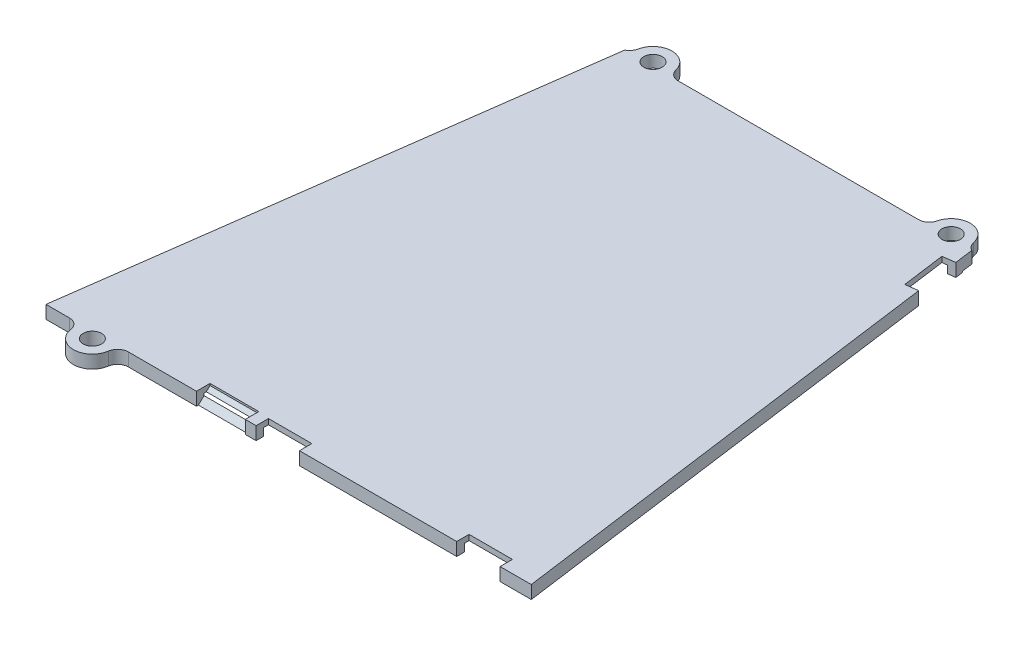
SolidWorks part; units mm, degrees
ref_plane "前视基准面" through (0, 0, 0) normal (0, 0, 1) x (1, 0, 0)
ref_plane "上视基准面" through (0, 0, 0) normal (0, 1, 0) x (1, 0, 0)
ref_plane "右视基准面" through (0, 0, 0) normal (1, 0, 0) x (0, 0, -1)
other "Configuration Table"
sketch "草图1" plane through (0, 0, 0) normal (0, 1, 0) x (1, 0, 0)
  line L0 (0, 0) -> (12.75, 94)
  line L1 (12.75, 94) -> (76.75, 94)
  line L2 (76.75, 94) -> (89.5, 0)
  line L3 (89.5, 0) -> (0, 0)
  line L4 (44.75, 94) -> (44.75, 0) construction
  dimension "D1" = 89.5
  dimension "D2" = 64
  dimension "D3" = 94
extrude "凸台-拉伸1" add sketch "草图1" along normal blind 1
sketch "草图2" plane through (0, 0, 0) normal (0, -1, 0) x (1, 0, 0)
  line L8 (87.8973, -1.4) -> (1.6027, -1.4)
  line L9 (1.6027, -1.4) -> (13.9729, -92.6)
  line L10 (13.9729, -92.6) -> (75.5271, -92.6)
  line L11 (75.5271, -92.6) -> (87.8973, -1.4)
  line L12 (87.8973, -1.4) -> (1.6027, -1.4)
  line L13 (1.6027, -1.4) -> (13.9729, -92.6)
  line L14 (13.9729, -92.6) -> (75.5271, -92.6)
  line L15 (75.5271, -92.6) -> (87.8973, -1.4)
  line L16 (89.5, 0) -> (0, 0)
  line L17 (0, 0) -> (12.75, -94)
  line L18 (12.75, -94) -> (76.75, -94)
  line L19 (76.75, -94) -> (89.5, 0)
  line L20 (89.5, 0) -> (0, 0)
  line L21 (0, 0) -> (12.75, -94)
  line L22 (12.75, -94) -> (76.75, -94)
  line L23 (76.75, -94) -> (89.5, 0)
  dimension "D1" = 1.4
  dimension "D2" = 0
extrude "凸台-拉伸2" add sketch "草图2" along normal blind 1.4
sketch "草图3" plane through (0, 1, 0) normal (0, 1, 0) x (1, 0, 0)
  line L0 (44.75, 0) -> (44.75, 94) construction
  line L1 (0, 0) -> (89.5, 0) construction
  line L2 (76.75, 94) -> (12.75, 94) construction
  line L3 (6.25, -1.2) -> (6.25, 0)
  line L4 (13.25, -1.2) -> (13.25, 0)
  line L5 (13.25, 0) -> (10.9542, 0)
  line L6 (8.5458, 0) -> (6.25, 0)
  line L7 (13.75, 94.7) -> (13.75, 94)
  line L8 (13.8207, 94) -> (15.7008, 94)
  line L9 (20.75, 94) -> (20.75, 94.7)
  line L10 (13.75, 94) -> (13.8207, 94)
  line L11 (18.7992, 94) -> (20.75, 94)
  line L12 (68.75, 94.7) -> (68.75, 94)
  line L13 (68.75, 94) -> (70.7008, 94)
  line L14 (75.75, 94) -> (75.75, 94.7)
  line L15 (73.7992, 94) -> (75.75, 94)
  arc A0 (8.5458, 0) -> (10.9542, 0) centre (9.75, -1.2) ccw
  arc A1 (6.25, -1.2) -> (13.25, -1.2) centre (9.75, -1.2) ccw
  arc A2 (18.7992, 94) -> (15.7008, 94) centre (17.25, 94.7) ccw
  arc A3 (20.75, 94.7) -> (13.75, 94.7) centre (17.25, 94.7) ccw
  arc A4 (73.7992, 94) -> (70.7008, 94) centre (72.25, 94.7) ccw
  arc A5 (75.75, 94.7) -> (68.75, 94.7) centre (72.25, 94.7) ccw
  dimension "D1" = 35
  dimension "D2" = 1.2
  dimension "D3" = 3.4
  dimension "D4" = 7
  dimension "D5" = 27.5
  dimension "D6" = 94.7
extrude "凸台-拉伸3" add sketch "草图3" against normal up to surface (2.4 mm away) up to face at (44.75, -1.4, -47)
sketch "草图4" plane through (0, 1, 0) normal (0, 1, 0) x (1, 0, 0)
  circle A0 centre (9.75, -1.2) radius 1.7
  circle A1 centre (17.25, 94.7) radius 1.7
  circle A2 centre (72.25, 94.7) radius 1.7
  arc A3 (73.7992, 94) -> (70.7008, 94) centre (72.25, 94.7) ccw construction
  arc A4 (18.7992, 94) -> (15.7008, 94) centre (17.25, 94.7) ccw construction
  arc A5 (8.5458, 0) -> (10.9542, 0) centre (9.75, -1.2) ccw construction
extrude "切除-拉伸2" cut sketch "草图4" against normal up to next
sketch "草图5" plane through (0, 1, 0) normal (0, 1, 0) x (1, 0, 0)
  line L0 (78.2124, 90.7412) -> (74.9423, 90.2977)
  line L1 (74.9423, 90.2977) -> (76.0176, 82.3703)
  line L2 (76.0176, 82.3703) -> (79.2876, 82.8138)
  line L3 (89.5, 0) -> (76.75, 94) construction
  line L4 (38.75, -1.2225) -> (38.75, 2.2775)
  line L5 (38.75, 2.2775) -> (46.75, 2.2775)
  line L6 (46.75, 2.2775) -> (46.75, -1.2225)
  line L7 (75.75, -1.2225) -> (75.75, 2.2775)
  line L8 (75.75, 2.2775) -> (83.75, 2.2775)
  line L9 (83.75, 2.2775) -> (83.75, -1.2225)
  arc A0 (38.75, -1.2225) -> (46.75, -1.2225) centre (42.75, -1.2225) ccw
  arc A1 (75.75, -1.2225) -> (83.75, -1.2225) centre (79.75, -1.2225) ccw
  arc A2 (79.2876, 82.8138) -> (78.2124, 90.7412) centre (78.75, 86.7775) ccw
  dimension "D1" = 8
  dimension "D2" = 3.3
  dimension "D3" = 3.5
extrude "切除-拉伸3" cut sketch "草图5" against normal blind 10
sketch "草图6" plane through (0, 0, 0) normal (1, 0, 0) x (0, 0, -1)
  line L0 (94.7, -1.4) -> (94.7, 1) construction
  line L1 (98.2, -1.4) -> (92, -1.4)
  line L2 (98.2, -1.4) -> (98.2, -1.2)
  line L3 (98.2, -1.2) -> (92, -1.2)
  line L4 (92, -1.4) -> (92, -1.2)
  line L5 (98.2, -1.4) -> (92, -1.2) construction
  line L6 (98.2, -1.2) -> (92, -1.4) construction
  point P4 (95.1, -1.3)
  dimension "D1" = 2.7
  dimension "D2" = 0.2
extrude "切除-拉伸4" cut sketch "草图6" along normal up to next
fillet "圆角1" radius 2 6 edges at (6.25, -0.2, 0) (13.25, -0.2, 0) (75.75, -0.1, -94) (68.75, -0.1, -94) (13.75, -0.1, -94) (20.75, -0.1, -94)
sketch "草图7" plane through (0, 1, 0) normal (0, 1, 0) x (1, 0, 0)
  line L0 (15.1915, 0) -> (38.75, 0) construction
  line L1 (27.75, 0) -> (36.75, 0)
  line L2 (27.75, 0) -> (27.75, 2.5)
  line L3 (27.75, 2.5) -> (36.75, 2.5)
  line L4 (36.75, 0) -> (36.75, 2.5)
  line L5 (27.75, 0) -> (36.75, 2.5) construction
  line L6 (27.75, 2.5) -> (36.75, 0) construction
  line L7 (38.75, 2.2775) -> (38.75, 0) construction
  point P4 (32.25, 1.25)
  dimension "D1" = 2
  dimension "D2" = 9
  dimension "D3" = 2.5
extrude "切除-拉伸5" cut sketch "草图7" against normal through all
sketch "草图8" plane through (36.75, 0, 0) normal (-1, 0, 0) x (0, 0, 1)
  line L0 (-2.5, 0.6534) -> (-1.8193, 0)
  line L1 (-0.361, -1.4) -> (-1.4, -1.4)
  line L2 (-1.4, -1.4) -> (-1.4, -0.4026)
  line L4 (-2.5, 0) -> (-2.5, 0.6534)
  line L5 (-2.5, 1) -> (0, -1.4) construction
  line L6 (-1.8193, 0) -> (-2.5, 0)
  line L7 (-1.4, -0.4026) -> (-0.361, -1.4)
  line L8 (-2.5, 0) -> (-1.4, 0) construction
  point P4 (-1.8173, 0)
  dimension "D1" = 0.5
extrude "凸台-拉伸4" add sketch "草图8" along normal up to next
